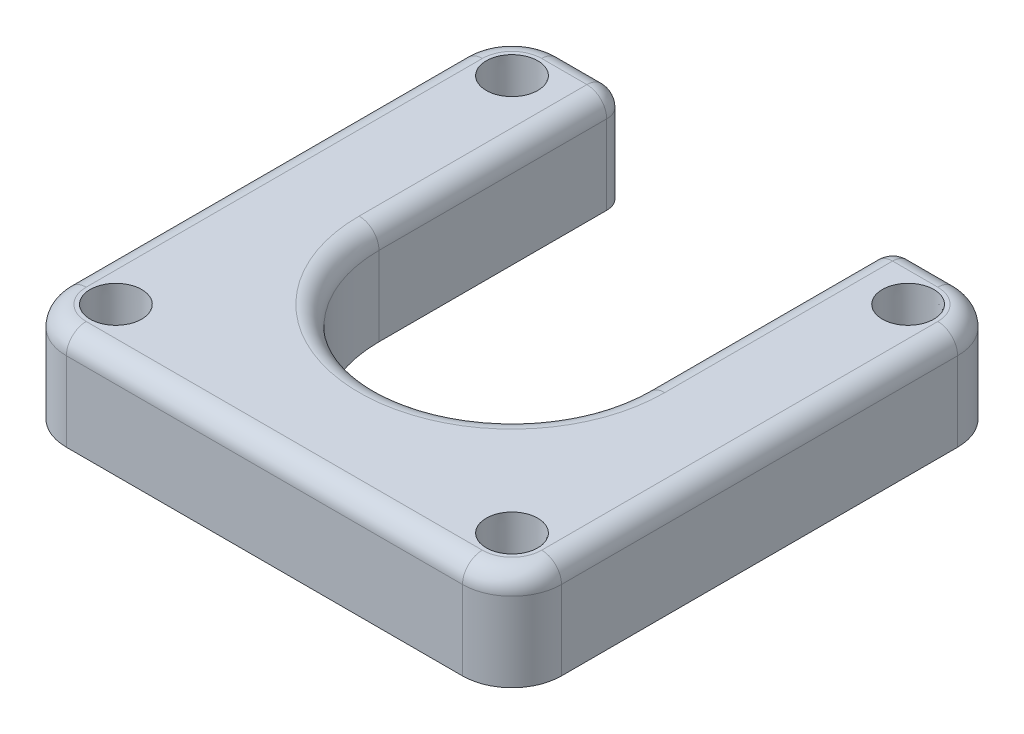
SolidWorks part; units mm, degrees
ref_plane "Front" through (0, 0, 0) normal (0, 0, 1) x (1, 0, 0)
ref_plane "Top" through (0, 0, 0) normal (0, 1, 0) x (1, 0, 0)
ref_plane "Right" through (0, 0, 0) normal (1, 0, 0) x (0, 0, -1)
sketch "Sketch1" plane through (0, 0, 0) normal (0, 1, 0) x (1, 0, 0)
  line L0 (-20, 20) -> (20, 20) construction
  line L1 (-20, -25) -> (20, -25)
  line L2 (-25, -20) -> (-25, 20)
  line L3 (-20, 25) -> (20, 25)
  line L4 (25, -20) -> (25, 20)
  line L5 (-25, -25) -> (25, 25) construction
  line L6 (-25, 25) -> (25, -25) construction
  line L7 (-50, 0) -> (50, 0) construction
  line L8 (-13.435, 0) -> (-13.435, 25)
  line L9 (13.435, 0) -> (13.435, 25)
  circle A0 centre (0, 0) radius 13.335 construction
  arc A1 (-13.435, 0) -> (13.435, 0) centre (0, 0) ccw
  circle A2 centre (-20, 20) radius 1.7
  circle A3 centre (20, 20) radius 1.7
  circle A4 centre (20, -20) radius 1.7
  circle A5 centre (-20, -20) radius 1.7
  circle A6 centre (0, 0) radius 13.435 construction
  circle A7 centre (-20, 20) radius 2.6
  circle A8 centre (20, 20) radius 2.6
  circle A9 centre (-20, -20) radius 2.6
  circle A10 centre (20, -20) radius 2.6
  arc A11 (20, 25) -> (25, 20) centre (20, 20) cw
  arc A12 (25, -20) -> (20, -25) centre (20, -20) cw
  arc A13 (-20, -25) -> (-25, -20) centre (-20, -20) cw
  arc A14 (-25, 20) -> (-20, 25) centre (-20, 20) cw
  dimension "D1" = 26.67
  dimension "D3" = 3.4
  dimension "D4" = 3.4
  dimension "D8" = 5.2
  dimension "D9" = 5.2
  dimension "D10" = 5
  dimension "D5" = 40
  dimension "D6" = 50
  dimension "D7" = 50
  dimension "D2" = 0.1
extrude "Boss-Extrude1" add sketch "Sketch1" along normal blind 10 contours L2 A14 L3 A11 L4 A12 L1 A13
extrude "Cut-Extrude1" cut sketch "Sketch1<4>" along normal through all contours L8 A1 L9 L3 | A2 | A5 | A4 | A3 region at (0, 0, -7.0976)
sketch "Sketch1<4>" plane through (0, 0, 0) normal (0, 1, 0) x (1, 0, 0) same geometry as "Sketch1"
extrude "Cut-Extrude2" cut sketch "Sketch1<5>" against normal blind 3.9 draft 1.5 from surface contours A7 | A8 | A9 | A10 starting at face at (20, 10, 18.3)
sketch "Sketch1<5>" plane through (0, 0, 0) normal (0, 1, 0) x (1, 0, 0) same geometry as "Sketch1"
fillet "Fillet1" radius 2 5 edges at (-13.435, 10, -12.5) (0, 10, 13.435) (-13.435, 5, -25) (13.435, 5, -25) (13.435, 10, -12.5)
fillet "Fillet2" radius 2 11 edges at (14.0208, 9.4142, -24.4142) (17.7175, 10, -25) (23.5355, 10, -23.5355) (25, 10, 0) (23.5355, 10, 23.5355) (0, 10, 25) (-23.5355, 10, 23.5355) (-14.0208, 9.4142, -24.4142) (-17.7175, 10, -25) (-23.5355, 10, -23.5355) (-25, 10, 0)
equation "\"D4@Sketch1\"=\"D3@Sketch1\""
equation "\"D9@Sketch1\"=\"D8@Sketch1\""
